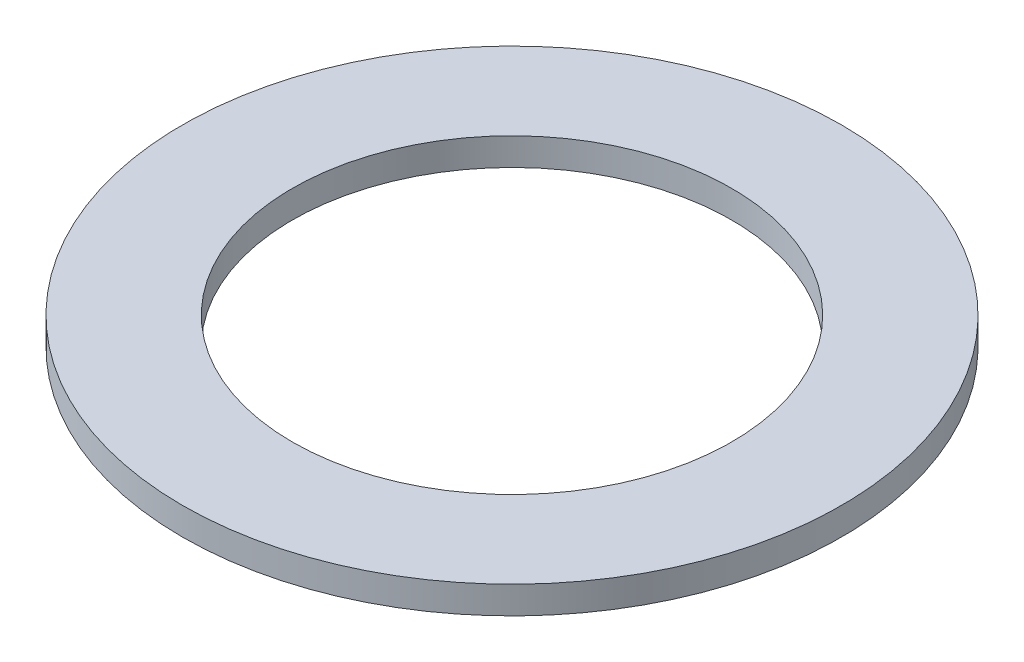
SolidWorks part; units mm, degrees
ref_plane "Front Plane" through (0, 0, 0) normal (0, 0, 1) x (1, 0, 0)
ref_plane "Top Plane" through (0, 0, 0) normal (0, 1, 0) x (1, 0, 0)
ref_plane "Right Plane" through (0, 0, 0) normal (1, 0, 0) x (0, 0, -1)
sketch "Sketch1" plane through (0, 0, 0) normal (0, 1, 0) x (1, 0, 0)
  circle A0 centre (0, 0) radius 60
  dimension "FLANGE_OD" = 120
extrude "Boss-Extrude1" add sketch "Sketch1" along normal blind 5
sketch "Sketch2" plane through (0, 0, 0) normal (0, 1, 0) x (1, 0, 0)
  circle A0 centre (0, 0) radius 40
  dimension "BORE_D" = 80
extrude "Cut-Extrude1" cut sketch "Sketch2" along normal through all
sketch "Sketch3" plane through (0, 5, 0) normal (0, 1, 0) x (1, 0, 0)
  circle A0 centre (0, 0) radius 21.795 construction
  circle A1 centre (-21.795, 0) radius 1.9833
  dimension "BOLT_D" = 3.9666
  dimension "BOLT_PCD" = 43.5899
extrude "Cut-Extrude2" cut sketch "Sketch3" against normal blind 4.8317 rebuild error yes
pattern_circular "CirPattern1" count 4 over 360 rebuild error yes
